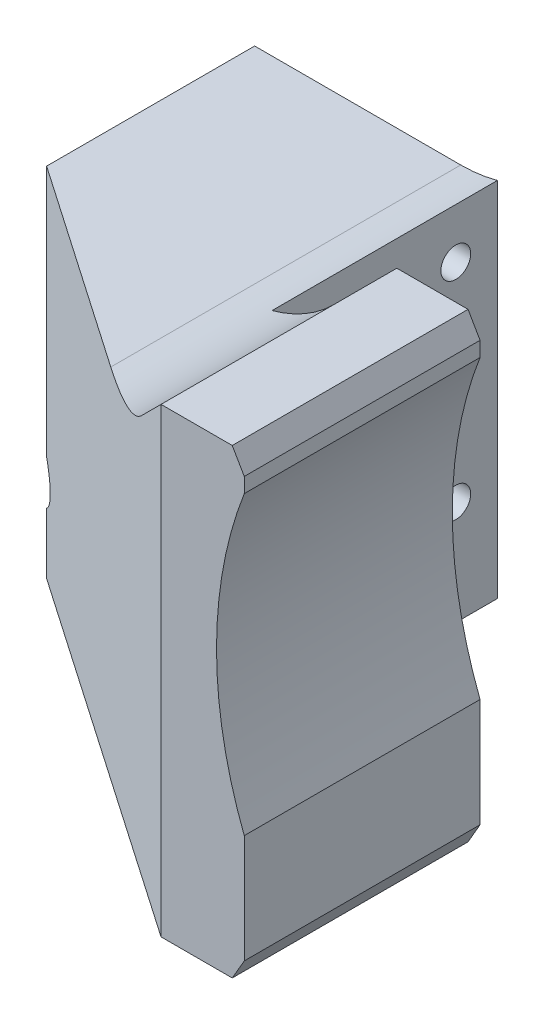
SolidWorks part; units mm, degrees
material "Rubber"
ref_plane "Front Plane" through (0, 0, 0) normal (0, 0, 1) x (1, 0, 0)
ref_plane "Top Plane" through (0, 0, 0) normal (0, 1, 0) x (1, 0, 0)
ref_plane "Right Plane" through (0, 0, 0) normal (1, 0, 0) x (0, 0, -1)
sketch "Sketch1" plane through (0, 0, 0) normal (0, 1, 0) x (1, 0, 0)
  line L0 (0, 0) -> (35, 0)
  line L1 (35, 0) -> (35, -32.5)
  line L2 (35, -32.5) -> (65, -32.5)
  line L3 (65, -32.5) -> (65, -66.5)
  line L4 (65, -66.5) -> (53, -66.5)
  line L5 (53, -66.5) -> (0, -30)
  line L6 (0, -30) -> (0, 0)
  dimension "D1" = 35
  dimension "D2" = 30
  dimension "D3" = 12
  dimension "D4" = 32.5
  dimension "D5" = 34
  dimension "D6" = 30
extrude "Boss-Extrude1" add sketch "Sketch1" along normal blind 51.5
sketch "Sketch3" plane through (35, 0, 0) normal (1, 0, 0) x (0, 0, -1)
  line L2 (-32.5, 0) -> (0, 0) construction
  circle A1 centre (-26.15, 12) radius 5
  dimension "D5" = 10
  dimension "D4" = 12
extrude "Cut-Extrude1" cut sketch "Sketch3" against normal through all
sketch "Sketch4" plane through (0, 0, 0) normal (0, 0, -1) x (-1, 0, 0)
  line L0 (0, 8) -> (-1, 8)
  line L1 (0, 51.5) -> (0, 0) construction
  line L2 (-6, 3) -> (-6, 0)
  line L3 (-35, 0) -> (0, 0) construction
  line L4 (-6, 0) -> (0, 0)
  line L5 (0, 0) -> (0, 8)
  arc A0 (-6, 3) -> (-1, 8) centre (-1, 3) cw
  point P11 (-6, 8)
  dimension "D3" = 5
  dimension "D1" = 8
  dimension "D2" = 6
extrude "Cut-Extrude2" [suppressed] cut sketch "Sketch4" against normal blind 10
sketch "Sketch5" plane through (0, 51.5, 0) normal (0, 1, 0) x (1, 0, 0)
  line L0 (65, -32.5) -> (35, -32.5) construction
  line L1 (65, -66.5) -> (53, -66.5)
  line L2 (65, -66.5) -> (65, -32.5)
  line L3 (65, -32.5) -> (53, -32.5)
  line L4 (53, -66.5) -> (53, -32.5)
extrude "Boss-Extrude2" add sketch "Sketch5" along normal blind 15
chamfer "Chamfer1" distance 15 angle 45 1 edges at (53, 51.5, 49.5)
sketch "Sketch6" plane through (0, 0, 66.5) normal (0, 0, 1) x (1, 0, 0)
  line L0 (65, 66.5) -> (65, 0) construction
  line L1 (53, 0) -> (65, 0) construction
  circle A0 centre (120, 40) radius 59
  dimension "D2" = 118
  dimension "D1" = 55
  dimension "D3" = 40
extrude "Cut-Extrude3" cut sketch "Sketch6" against normal through all
sketch "Sketch7" plane through (0, 0, 0) normal (-1, 0, 0) x (0, 0, 1)
  line L0 (0, 51.5) -> (0, 0) construction
  line L1 (0, 0) -> (30, 0) construction
  circle A0 centre (6, 15) radius 2.15
  circle A1 centre (6, 45) radius 2.15
  dimension "D1" = 4.3
  dimension "D5" = 4.3
  dimension "D2" = 6
  dimension "D3" = 15
  dimension "D4" = 45
extrude "Cut-Extrude4" cut sketch "Sketch7" against normal through all
sketch "Sketch8" plane through (0, 0, 0) normal (-1, 0, 0) x (0, 0, 1)
  line L0 (0, 51.5) -> (0, 0) construction
  circle A0 centre (6, 45) radius 4.5
  circle A1 centre (6, 15) radius 4.5
  dimension "D1" = 9
  dimension "D2" = 9
extrude "Cut-Extrude5" cut sketch "Sketch8" against normal blind 25
fillet "Fillet1" radius 20 1 edges at (38, 51.5, 44.3349)
chamfer "Chamfer3" distance 3 angle 30 2 edges at (65, 0, 49.5) (65, 66.5, 49.5) first distance on face at (65, 9.3229, 49.5) first distance on face at (65, 63.9271, 49.5)
